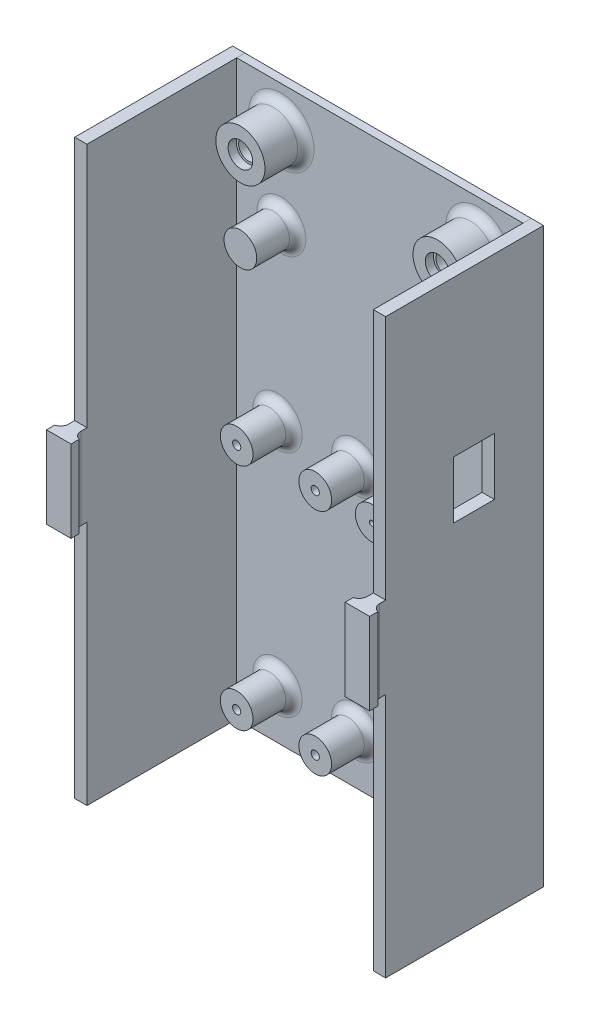
SolidWorks part; units mm, degrees
ref_plane "Přední rovina" through (0, 0, 0) normal (0, 0, 1) x (1, 0, 0)
ref_plane "Horní rovina" through (0, 0, 0) normal (0, 1, 0) x (1, 0, 0)
ref_plane "Pravá rovina" through (0, 0, 0) normal (1, 0, 0) x (0, 0, -1)
sketch "Skica1" plane through (0, 0, 0) normal (0, 0, 1) x (1, 0, 0)
  line L1 (0, 0) -> (70, 0)
  line L2 (0, 0) -> (0, 140)
  line L3 (0, 140) -> (70, 140)
  line L4 (70, 0) -> (70, 140)
  dimension "D1" = 140
  dimension "D2" = 70
extrude "Přidat vysunutím1" add sketch "Skica1" along normal blind 2
sketch "Skica2" plane through (0, 0, 2) normal (0, 0, 1) x (1, 0, 0)
  line L1 (70, 140) -> (0, 140) construction
  line L5 (0, 140) -> (0, 0) construction
  line L9 (70, 0) -> (70, 140) construction
  line L10 (0, 0) -> (70, 0) construction
  circle A0 centre (59.1, 130) radius 2.425
  circle A1 centre (10.9, 130) radius 2.425
  circle A2 centre (10, 68) radius 1
  circle A3 centre (29.2, 68) radius 1
  circle A4 centre (10, 12) radius 1
  circle A5 centre (29.2, 12) radius 1
  circle A6 centre (43, 68) radius 0.6
  circle A7 centre (60, 68) radius 0.6
  circle A8 centre (60, 42) radius 0.6
  circle A9 centre (55, 30) radius 0.6
  circle A10 centre (10, 68) radius 4
  circle A11 centre (29.2, 68) radius 4
  circle A12 centre (43, 68) radius 4
  circle A13 centre (60, 68) radius 4
  circle A14 centre (60, 42) radius 4
  circle A15 centre (55, 30) radius 4
  circle A16 centre (29.2, 12) radius 4
  circle A17 centre (10, 12) radius 4
  circle A18 centre (10.9, 130) radius 6
  circle A19 centre (59.1, 130) radius 6
  circle A20 centre (43, 42) radius 0.6
  circle A21 centre (43, 42) radius 4
  circle A22 centre (10.9, 110) radius 4
  circle A23 centre (59.1, 110) radius 4
  circle A24 centre (60, 14) radius 4
  dimension "D1" = 4.85
  dimension "D2" = 4.85
  dimension "D3" = 48.2
  dimension "D5" = 10.9
  dimension "D6" = 10
  dimension "D7" = 2
  dimension "D8" = 2
  dimension "D9" = 1.2
  dimension "D10" = 1.2
  dimension "D11" = 1.2
  dimension "D12" = 2
  dimension "D13" = 2
  dimension "D14" = 56
  dimension "D15" = 56
  dimension "D16" = 10
  dimension "D17" = 62
  dimension "D18" = 19.2
  dimension "D19" = 19.2
  dimension "D20" = 10
  dimension "D21" = 12
  dimension "D22" = 26
  dimension "D23" = 0
  dimension "D24" = 17
  dimension "D25" = 10
  dimension "D26" = 62
  dimension "D27" = 42
  dimension "D28" = 30
  dimension "D29" = 1.2
  dimension "D30" = 15
  dimension "D31" = 8
  dimension "D32" = 8
  dimension "D33" = 8
  dimension "D34" = 8
  dimension "D35" = 8
  dimension "D36" = 8
  dimension "D37" = 8
  dimension "D38" = 8
  dimension "D39" = 12
  dimension "D40" = 12
  dimension "D42" = 1.2
  dimension "D43" = 8
  dimension "D44" = 17
  dimension "D45" = 26
  dimension "D46" = 8
  dimension "D47" = 8
  dimension "D48" = 20
  dimension "D49" = 20
  dimension "D50" = 48.2
  dimension "D51" = 10.9
  dimension "D52" = 8
  dimension "D53" = 10
  dimension "D54" = 14
  dimension "D41" = 62
extrude "Přidat vysunutím2" add sketch "Skica2" along normal blind 10
sketch "Skica4" plane through (0, 0, 0) normal (0, 0, 1) x (1, 0, 0)
  line L1 (0, 0) -> (-3, 0)
  line L2 (0, 0) -> (0, 140)
  line L3 (0, 140) -> (-3, 140)
  line L4 (-3, 0) -> (-3, 140)
  line L25 (35, 128.5362) -> (35, -20.7413) construction
  line L34 (73, 0) -> (73, 140)
  line L52 (70, 140) -> (73, 140)
  line L53 (70, 0) -> (70, 140)
  line L54 (70, 0) -> (73, 0)
  dimension "D4" = 140
  dimension "D12" = 35
  dimension "D14" = 3
extrude "Přidat vysunutím3" add sketch "Skica4" along normal blind 42 separate body contours L4 L1 L3 | L52 L54 region at (-1.5, 70, 0) region at (71.5, 70, 0)
sketch "Skica5" plane through (73, 0, 0) normal (1, 0, 0) x (0, 0, -1)
  line L0 (0, 0) -> (0, 140) construction
  line L1 (-22, 88) -> (-12, 88)
  line L2 (-22, 88) -> (-22, 102)
  line L3 (-22, 102) -> (-12, 102)
  line L4 (-12, 88) -> (-12, 102)
  line L5 (-22, 102) -> (-12, 102)
  line L6 (0, 140) -> (-42, 140) construction
  dimension "D1" = 38
  dimension "D2" = 14
  dimension "D3" = 10
  dimension "D4" = 12
extrude "Odebrat vysunutím2" cut sketch "Skica5" against normal blind 20 contours L3 L4 L1 L2
fillet "Zaoblit1" radius 2 14 edges at (6, 12, 2) (25.2, 12, 2) (51, 30, 2) (56, 42, 2) (4.9, 130, 2) (53.1, 130, 2) (56, 68, 2) (39, 68, 2) (25.2, 68, 2) (6, 68, 2) (39, 42, 2) (56, 14, 2) (55.1, 110, 2) (6.9, 110, 2)
sketch "Skica7" plane through (0, 0, 0) normal (0, -1, 0) x (1, 0, 0)
  line L0 (0, 42) -> (0, 0) construction
  line L1 (1.5, 42) -> (-4.5, 42)
  line L2 (1.5, 42) -> (1.5, 44)
  line L3 (1.5, 44) -> (-4.5, 44)
  line L4 (-4.5, 42) -> (-4.5, 44)
  line L10 (35, 57.629) -> (35, -12.1968) construction
  line L11 (74.5, 42) -> (74.5, 44)
  line L12 (68.5, 44) -> (74.5, 44)
  line L13 (68.5, 42) -> (68.5, 44)
  line L14 (68.5, 42) -> (74.5, 42)
  line L16 (0, 42) -> (-3, 42) construction
  dimension "D1" = 1.5
  dimension "D2" = 0
  dimension "D3" = 2
  dimension "D4" = 6
  dimension "D5" = 35
extrude "Přidat vysunutím4" add sketch "Skica7" against normal blind 140
fillet "Zaoblit2" radius 2 2 edges at (-3, 70, 42) (0, 70, 42)
fillet "Zaoblit3" radius 2 2 edges at (73, 70, 42) (70, 70, 42)
sketch "Skica8" plane through (0, 0, 12) normal (0, 0, 1) x (1, 0, 0)
  circle A0 centre (55, 30) radius 4
  circle A1 centre (60, 14) radius 4
  point P18 (55, 30)
  dimension "D1" = 8
  dimension "D2" = 8
extrude "Odebrat vysunutím3" cut sketch "Skica8" against normal blind 4
sketch "Skica9" plane through (0, 0, 0) normal (0, -1, 0) x (1, 0, 0)
  line L1 (-10.0634, 48.6) -> (7.9366, 48.6)
  line L2 (-10.0634, 48.6) -> (-10.0634, 38.6)
  line L3 (-10.0634, 38.6) -> (7.9366, 38.6)
  line L4 (7.9366, 48.6) -> (7.9366, 38.6)
  line L5 (62.06, 48.6) -> (80.06, 48.6)
  line L6 (62.06, 48.6) -> (62.06, 38.6)
  line L7 (62.06, 38.6) -> (80.06, 38.6)
  line L8 (80.06, 48.6) -> (80.06, 38.6)
  line L9 (0, 40.0635) -> (0, 0) construction
  line L10 (70, 40.0635) -> (70, 0) construction
  line L11 (0, 2) -> (70, 2) construction
  dimension "D1" = 10
  dimension "D2" = 18
  dimension "D3" = 36.6
  dimension "D4" = 7.9366
  dimension "D5" = 7.94
  dimension "D6" = 18
  dimension "D7" = 10
  dimension "D8" = 36.6
extrude "Odebrat vysunutím4" cut sketch "Skica9" against normal blind 60
sketch "Skica10" plane through (0, 140, 0) normal (0, 1, 0) x (1, 0, 0)
  line L0 (70, -2) -> (0, -2) construction
  line L1 (-10.06, -38.6) -> (7.94, -38.6)
  line L2 (-10.06, -38.6) -> (-10.06, -48.6)
  line L3 (-10.06, -48.6) -> (7.94, -48.6)
  line L4 (7.94, -38.6) -> (7.94, -48.6)
  line L5 (0, -40.0635) -> (0, 0) construction
  line L6 (70, -40.0635) -> (70, 0) construction
  line L7 (62.06, -38.6) -> (80.06, -38.6)
  line L8 (62.06, -38.6) -> (62.06, -48.6)
  line L9 (62.06, -48.6) -> (80.06, -48.6)
  line L10 (80.06, -38.6) -> (80.06, -48.6)
  dimension "D1" = 36.6
  dimension "D2" = 10
  dimension "D3" = 18
  dimension "D4" = 7.94
  dimension "D5" = 7.94
  dimension "D6" = 10
  dimension "D7" = 18
  dimension "D8" = 36.6
extrude "Odebrat vysunutím5" cut sketch "Skica10" against normal blind 60
sketch "Skica11" plane through (0, 0, 12) normal (0, 0, 1) x (1, 0, 0)
  circle A0 centre (10.9, 130) radius 3
  circle A1 centre (59.1, 130) radius 3
  dimension "D1" = 6
  dimension "D2" = 6
extrude "Odebrat vysunutím6" cut sketch "Skica11" against normal blind 2
